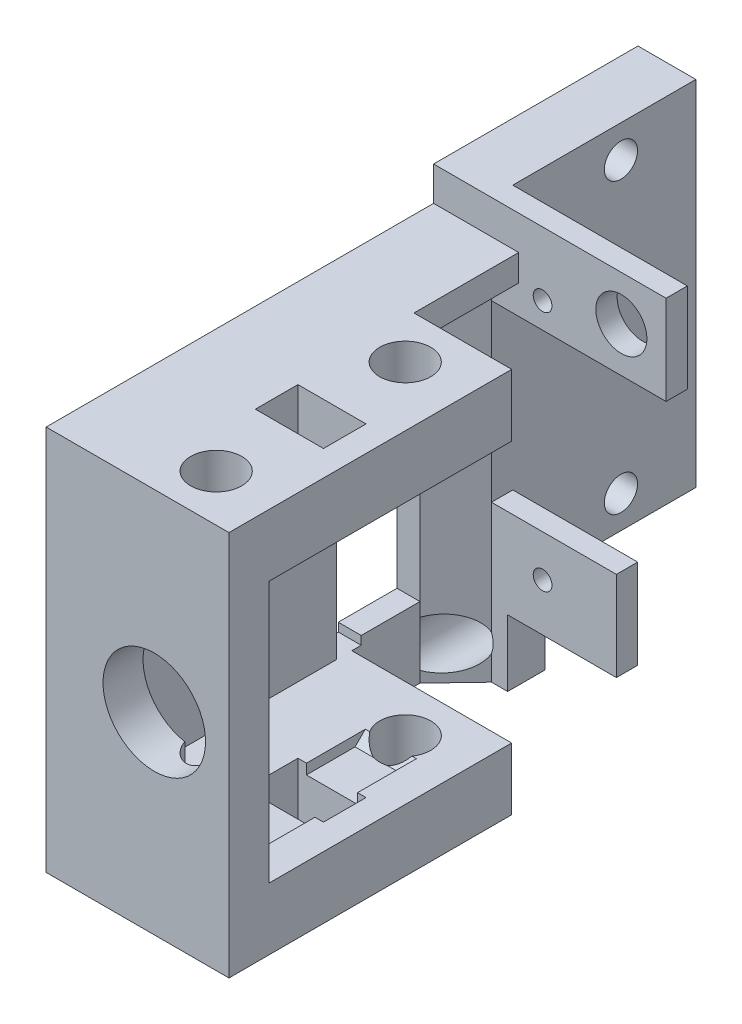
SolidWorks part; units mm, degrees
ref_plane "Alzado" through (0, 0, 0) normal (0, 0, 1) x (1, 0, 0)
ref_plane "Planta" through (0, 0, 0) normal (0, 1, 0) x (1, 0, 0)
ref_plane "Vista lateral" through (0, 0, 0) normal (1, 0, 0) x (0, 0, -1)
sketch "Croquis4" plane through (0, 0, 0) normal (1, 0, 0) x (0, 0, -1)
  line L1 (22.75, 22.65) -> (-22.75, 22.65)
  line L2 (22.75, 22.65) -> (22.75, -22.65)
  line L3 (22.75, -22.65) -> (-22.75, -22.65)
  line L4 (-22.75, 22.65) -> (-22.75, -22.65)
  line L5 (22.75, 22.65) -> (-22.75, -22.65) construction
  line L6 (22.75, -22.65) -> (-22.75, 22.65) construction
  point P0 (0, 0)
  dimension "D1" = 45.5
  dimension "D2" = 45.3
extrude "Saliente-Extruir3" add sketch "Croquis4" along normal blind 21.47
sketch "Croquis5" plane through (21.47, 0, 0) normal (1, 0, 0) x (0, 0, -1)
  line L0 (22.75, 22.65) -> (-22.75, 22.65) construction
  line L1 (23.0917, 15.35) -> (-18.05, 15.35)
  line L2 (23.0917, 15.35) -> (23.0917, -15.35)
  line L3 (23.0917, -15.35) -> (-18.05, -15.35)
  line L4 (-18.05, 15.35) -> (-18.05, -15.35)
  line L5 (23.0917, 15.35) -> (-18.05, -15.35) construction
  line L6 (23.0917, -15.35) -> (-18.05, 15.35) construction
  line L7 (-22.75, 22.65) -> (-22.75, -22.65) construction
  line L8 (-22.75, -22.65) -> (22.75, -22.65) construction
  point P0 (2.5209, 0)
  dimension "D1" = 7.3
  dimension "D2" = 4.7
  dimension "D3" = 7.3
extrude "Cortar-Extruir2" cut sketch "Croquis5" against normal blind 18.77
sketch "Croquis6" plane through (0, 22.65, 0) normal (0, 1, 0) x (1, 0, 0)
  line L0 (21.47, 22.75) -> (0, 22.75) construction
  line L1 (30.77, 35.05) -> (12.17, 35.05)
  line L2 (30.77, 35.05) -> (30.77, 10.45)
  line L3 (30.77, 10.45) -> (12.17, 10.45)
  line L4 (12.17, 35.05) -> (12.17, 10.45)
  line L5 (30.77, 35.05) -> (12.17, 10.45) construction
  line L6 (30.77, 10.45) -> (12.17, 35.05) construction
  line L7 (21.47, 22.75) -> (21.47, -22.75) construction
  point P0 (21.47, 22.75)
  dimension "D1" = 12.3
  dimension "D2" = 9.3
extrude "Cortar-Extruir3" cut sketch "Croquis6" against normal blind 18.77
sketch "Croquis7" plane through (0, 22.65, 0) normal (0, 1, 0) x (1, 0, 0)
  line L0 (21.47, -22.75) -> (0, -22.75) construction
  line L1 (21.47, 10.45) -> (21.47, -22.75) construction
  line L2 (12.17, 10.45) -> (21.47, 10.45) construction
  circle A0 centre (14.47, -17.25) radius 3
  circle A1 centre (14.47, 4.95) radius 3
  dimension "D4" = 6
  dimension "D5" = 6
  dimension "D1" = 5.5
  dimension "D2" = 7
  dimension "D3" = 5.5
extrude "Cortar-Extruir4" cut sketch "Croquis7" against normal blind 58.77
sketch "Croquis8" plane through (0, 0, 22.75) normal (0, 0, 1) x (1, 0, 0)
  line L0 (0, 22.65) -> (0, -22.65) construction
  circle A0 centre (12.7, 0) radius 6.02
  dimension "D2" = 12.04
  dimension "D1" = 12.7
extrude "Cortar-Extruir5" cut sketch "Croquis8" against normal blind 58.77
sketch "Croquis9" plane through (0, 15.35, 0) normal (0, -1, 0) x (1, 0, 0)
  line L0 (14.47, -4.95) -> (14.47, 17.0717) construction
  line L1 (17.47, 17.25) -> (17.47, -4.95) construction
  line L2 (17.47, -4.95) -> (11.47, -4.95) construction
  line L3 (11.47, -4.95) -> (11.47, 17.25) construction
  line L4 (11.47, 17.25) -> (17.47, 17.25) construction
  line L6 (17.47, 14.2208) -> (11.47, 14.2208)
  line L7 (17.47, 14.2208) -> (17.47, -2.0991)
  line L8 (17.47, -2.0991) -> (11.47, -2.0991)
  line L9 (11.47, 14.2208) -> (11.47, -2.0991)
  line L10 (17.47, 14.2208) -> (11.47, -2.0991) construction
  line L11 (17.47, -2.0991) -> (11.47, 14.2208) construction
  arc A0 (11.5786, 18.05) -> (17.3614, 18.05) centre (14.47, 17.25) ccw construction
  circle A1 centre (14.47, -4.95) radius 3 construction
  point P10 (14.47, 6.0608)
extrude "Cortar-Extruir7" cut sketch "Croquis9" against normal blind 1.2
chamfer "Chaflán1" distance 1.2 angle 45 3 edges at (16.437, 15.35, -2.0991) (12.503, 15.35, -2.0991) (14.47, 15.35, 14.2208)
sketch "Croquis10" plane through (0, 22.65, 0) normal (0, 1, 0) x (1, 0, 0)
  line L0 (14.47, 4.95) -> (14.47, -17.25) construction
  line L1 (14.47, -17.25) -> (11.47, -17.25) construction
  line L2 (11.47, -17.25) -> (11.47, 4.95) construction
  line L3 (11.47, 4.95) -> (17.47, 4.95) construction
  line L4 (17.47, 4.95) -> (17.47, -17.25) construction
  line L5 (17.47, -17.25) -> (14.47, -17.25) construction
  line L7 (18.47, -8.65) -> (10.47, -8.65)
  line L8 (18.47, -8.65) -> (18.47, -3.65)
  line L9 (18.47, -3.65) -> (10.47, -3.65)
  line L10 (10.47, -8.65) -> (10.47, -3.65)
  line L11 (18.47, -8.65) -> (10.47, -3.65) construction
  line L12 (18.47, -3.65) -> (10.47, -8.65) construction
  circle A0 centre (14.47, -17.25) radius 3 construction
  circle A1 centre (14.47, 4.95) radius 3 construction
  point P4 (14.47, -6.15)
  dimension "D1" = 5
  dimension "D2" = 8
extrude "Cortar-Extruir8" cut sketch "Croquis10" against normal blind 71.2
sketch "Croquis11" plane through (0, -15.35, 0) normal (0, 1, 0) x (1, 0, 0)
  line L0 (17.47, 4.95) -> (17.47, -17.25) construction
  line L1 (17.47, -17.25) -> (11.47, -17.25) construction
  line L2 (11.47, -17.25) -> (11.47, 4.95) construction
  line L3 (11.47, 4.95) -> (14.47, 4.95) construction
  line L4 (14.47, 4.95) -> (14.47, -17.25) construction
  line L6 (17.47, -14.3591) -> (11.47, -14.3591)
  line L7 (17.47, -14.3591) -> (17.47, 2.0591)
  line L8 (17.47, 2.0591) -> (11.47, 2.0591)
  line L9 (11.47, -14.3591) -> (11.47, 2.0591)
  line L10 (17.47, -14.3591) -> (11.47, 2.0591) construction
  line L11 (17.47, 2.0591) -> (11.47, -14.3591) construction
  circle A0 centre (14.47, 4.95) radius 3 construction
  arc A1 (17.3614, -18.05) -> (11.5786, -18.05) centre (14.47, -17.25) ccw construction
  point P9 (14.47, -6.15)
extrude "Cortar-Extruir9" cut sketch "Croquis11" against normal blind 1.2
chamfer "Chaflán2" distance 1.2 angle 45 4 edges at (12.5692, -15.35, -2.0591) (16.3708, -15.35, -2.0591) (12.5692, -15.35, 14.3591) (16.3708, -15.35, 14.3591)
sketch "Croquis12" plane through (2.7, 0, 0) normal (1, 0, 0) x (0, 0, -1)
  line L0 (8.65, 15.35) -> (8.65, -15.35)
  line L1 (22.75, 15.35) -> (-18.05, 15.35) construction
  line L2 (-18.05, -15.35) -> (22.75, -15.35) construction
  line L3 (-18.05, 15.35) -> (-18.05, -15.35) construction
  line L4 (8.65, -15.35) -> (11.5547, -15.35)
  line L5 (-18.05, -15.35) -> (22.75, -15.35) construction
  line L6 (11.5547, -15.35) -> (11.5547, -14.35)
  line L7 (11.5547, -14.35) -> (18.45, -14.35)
  line L8 (18.45, -14.35) -> (18.45, 15.35)
  line L9 (22.75, 15.35) -> (10.45, 15.35) construction
  line L10 (18.45, 15.35) -> (8.65, 15.35)
  line L11 (22.75, 15.35) -> (22.75, -15.35) construction
  dimension "D1" = 26.7
  dimension "D2" = 2.9047
  dimension "D3" = 4.3
  dimension "D4" = 1
extrude "Cortar-Extruir12" cut sketch "Croquis12" against normal blind 11.2
sketch "Croquis14" plane through (2.7, 0, 0) normal (1, 0, 0) x (0, 0, -1)
  line L0 (22.75, 15.35) -> (10.15, 15.35) construction
  line L1 (22.75, 15.35) -> (22.75, -15.35) construction
  line L2 (8.65, 15.35) -> (-18.05, 15.35) construction
  line L3 (10.15, 15.35) -> (5.15, 15.35)
  line L4 (5.15, 15.35) -> (10.15, 20.35)
  line L5 (10.15, 20.35) -> (10.15, 15.35)
  dimension "D1" = 12.6
  dimension "D2" = 0
  dimension "D3" = 5
  dimension "D4" = 5
extrude "Cortar-Extruir14" cut sketch "Croquis14" along normal blind 7
sketch "Croquis15" plane through (12.17, 0, 0) normal (1, 0, 0) x (0, 0, -1)
  line L0 (22.75, 22.65) -> (22.75, 15.35) construction
  line L1 (10.45, 15.35) -> (22.75, 15.35)
  line L2 (10.45, 15.35) -> (10.45, 19.55)
  line L3 (10.45, 19.55) -> (22.75, 19.55)
  line L4 (22.75, 15.35) -> (22.75, 19.55)
  line L5 (22.75, 22.65) -> (10.45, 22.65) construction
  dimension "D1" = 3.1
extrude "Cortar-Extruir15" cut sketch "Croquis15" against normal up to surface (9.47 mm away) up to face at (2.7, -4.7833, -17.5849)
sketch "Croquis16" plane through (0, 0, -10.15) normal (0, 0, 1) x (1, 0, 0)
  line L4 (2.7, 20.35) -> (2.7, 15.35)
  line L5 (2.7, 15.35) -> (9.7, 15.35)
  line L6 (9.7, 15.35) -> (9.7, 20.35)
  line L7 (9.7, 20.35) -> (2.7, 20.35)
  line L8 (2.7, 20.35) -> (2.7, 15.35)
  line L9 (2.7, 15.35) -> (9.7, 15.35)
  line L10 (9.7, 15.35) -> (9.7, 20.35)
  line L11 (9.7, 20.35) -> (2.7, 20.35)
  dimension "D1" = 0
extrude "Cortar-Extruir17" cut sketch "Croquis16" against normal up to surface (0.3 mm away) contours L8 L9 L10 L11 up to face at (12.1133, 19.1833, -10.45)
sketch "Croquis17" plane through (0, 0, -10.45) normal (0, 0, -1) x (-1, 0, 0)
  line L4 (-9.7, 19.55) -> (-2.7, 19.55)
  line L5 (-9.7, 20.35) -> (-9.7, 19.55)
  line L6 (-2.7, 20.35) -> (-9.7, 20.35)
  line L7 (-2.7, 19.55) -> (-2.7, 20.35)
  line L8 (-9.7, 19.55) -> (-2.7, 19.55)
  line L9 (-9.7, 20.35) -> (-9.7, 19.55)
  line L10 (-2.7, 20.35) -> (-9.7, 20.35)
  line L11 (-2.7, 19.55) -> (-2.7, 20.35)
  dimension "D1" = 0
extrude "Saliente-Extruir4" add sketch "Croquis17" against normal blind 3
sketch "Croquis18" plane through (0, 19.55, 0) normal (0, -1, 0) x (1, 0, 0)
  line L1 (2.7, -22.75) -> (24.5194, -22.75)
  line L2 (2.7, -22.75) -> (2.7, -10.45)
  line L3 (2.7, -10.45) -> (24.5194, -10.45)
  line L4 (24.5194, -22.75) -> (24.5194, -10.45)
  point P5 (24.5194, -11.6139)
  dimension "D1" = 12.3
extrude "Cortar-Extruir18" cut sketch "Croquis18" along normal blind 53
sketch "Croquis19" plane through (2.7, 0, 0) normal (1, 0, 0) x (0, 0, -1)
  line L0 (18.45, -14.35) -> (11.5547, -14.35) construction
  line L1 (11.5547, -14.35) -> (11.5547, -15.35) construction
  line L2 (11.5547, -15.35) -> (18.45, -15.35) construction
  line L3 (18.45, -15.35) -> (18.45, -14.35) construction
  line L4 (18.45, -14.35) -> (18.45, -14.85) construction
  line L5 (18.45, -14.85) -> (11.5547, -14.85) construction
  line L6 (18.45, -14.85) -> (53.9616, -14.85) construction
  line L7 (22.75, 18.5445) -> (22.75, -14.85) construction
  line L8 (22.75, 19.55) -> (22.75, -22.65) construction
  line L9 (22.75, -14.85) -> (53.9616, -14.85) construction
  line L11 (22.75, -14.85) -> (46.75, -14.85)
  line L12 (22.75, -14.85) -> (22.75, 26.65)
  line L13 (22.75, 26.65) -> (46.75, 26.65)
  line L14 (46.75, -14.85) -> (46.75, 26.65)
  dimension "D1" = 41.5
  dimension "D2" = 24
extrude "Saliente-Extruir5" add sketch "Croquis19" along normal blind 4.1 and the other way up to surface (2.7 mm away) other way up to face at (0, -4.7833, -12.8849)
sketch "Croquis21" plane through (6.8, 0, 0) normal (1, 0, 0) x (0, 0, -1)
  line L1 (22.75, 26.65) -> (25.25, 26.65)
  line L2 (22.75, 26.65) -> (22.75, 16.15)
  line L3 (22.75, 16.15) -> (25.25, 16.15)
  line L4 (25.25, 26.65) -> (25.25, 16.15)
  line L5 (22.75, -14.85) -> (25.25, -14.85)
  line L6 (22.75, -14.85) -> (22.75, -4.35)
  line L7 (22.75, -4.35) -> (25.25, -4.35)
  line L8 (25.25, -14.85) -> (25.25, -4.35)
  dimension "D1" = 2.5
  dimension "D2" = 10.5
  dimension "D3" = 2.5
  dimension "D4" = 10.5
extrude "Saliente-Extruir6" add sketch "Croquis21" along normal blind 20.5
sketch "Croquis22" plane through (6.8, 0, 0) normal (1, 0, 0) x (0, 0, -1)
  line L0 (46.75, -14.85) -> (46.75, 26.65) construction
  line L2 (46.75, 26.65) -> (25.25, 26.65) construction
  line L3 (25.25, -14.85) -> (46.75, -14.85) construction
  circle A0 centre (37.95, 22.85) radius 1.95
  circle A1 centre (37.95, -11.05) radius 1.95
  dimension "D1" = 3.9
  dimension "D5" = 3.9
  dimension "D2" = 8.8
  dimension "D3" = 3.8
  dimension "D4" = 3.8
extrude "Cortar-Extruir19" cut sketch "Croquis22" against normal blind 20.5
sketch "Croquis23" plane through (0, 0, -10.45) normal (0, 0, -1) x (-1, 0, 0)
  line L0 (-21.47, -15.35) -> (-21.47, -22.65) construction
  line L1 (-21.47, -22.2717) -> (-31.2653, -22.2717)
  line L2 (-21.47, -22.2717) -> (-21.47, -1.4695)
  line L3 (-21.47, -1.4695) -> (-31.2653, -1.4695)
  line L4 (-31.2653, -22.2717) -> (-31.2653, -1.4695)
extrude "Cortar-Extruir20" cut sketch "Croquis23" along normal blind 20.5
sketch "Croquis24" plane through (0, 0, -25.25) normal (0, 0, -1) x (-1, 0, 0)
  line L0 (-21.47, -14.85) -> (-21.47, -4.35) construction
  line L1 (-21.47, -14.85) -> (-6.8, -14.85) construction
  line L3 (-27.3, 16.15) -> (-6.8, 16.15) construction
  line L4 (-6.8, 16.15) -> (-6.8, 26.65) construction
  line L5 (-6.8, -14.85) -> (-6.8, -4.35) construction
  circle A0 centre (-12.8, -9.25) radius 1.1
  circle A1 centre (-12.8, 19.15) radius 1.1
  dimension "D3" = 2.2
  dimension "D4" = 2.2
  dimension "D1" = 8.67
  dimension "D2" = 5.6
  dimension "D5" = 3
  dimension "D6" = 6
  dimension "D7" = 6
extrude "Cortar-Extruir22" cut sketch "Croquis24" against normal up to surface (2.5 mm away) up to face at (11.74, 10.9667, -22.75)
sketch "Croquis25" plane through (0, 19.55, 0) normal (0, -1, 0) x (1, 0, 0)
  line L0 (2.7, -22.75) -> (2.7, -9.35) construction
  line L1 (12.17, -10.45) -> (10, -10.45)
  line L2 (12.17, -10.45) -> (12.17, -22.75)
  line L3 (12.17, -22.75) -> (10, -22.75)
  line L4 (10, -10.45) -> (10, -22.75)
  line L5 (2.7, -22.75) -> (11.7753, -22.75) construction
  dimension "D1" = 7.3
  dimension "D2" = 0
extrude "Cortar-Extruir23" cut sketch "Croquis25" against normal blind 13
sketch "Croquis26" plane through (0, 0, -25.25) normal (0, 0, -1) x (-1, 0, 0)
  line L1 (-27.3, 26.65) -> (-6.8, 26.65) construction
  line L2 (-27.3, 16.15) -> (-27.3, 26.65) construction
  circle A0 centre (-22.05, 21.4) radius 3
  point P2 (0, 0)
  point P5 (0, 0)
  dimension "D1" = 6
  dimension "D2" = 5.25
  dimension "D3" = 5.25
extrude "Cortar-Extruir24" cut sketch "Croquis26" against normal up to surface (2.5 mm away) up to face at (11.3783, 10.9667, -22.75)
sketch "Croquis27" plane through (2.7, 0, 0) normal (1, 0, 0) x (0, 0, -1)
  line L0 (18.45, 15.35) -> (18.45, 19.55) construction
  line L1 (22.75, 19.55) -> (9.35, 19.55) construction
sketch "Croquis28" plane through (0, 0, -22.75) normal (0, 0, 1) x (1, 0, 0)
  line L0 (6.8, 16.15) -> (6.8, 19.55) construction
  line L1 (2.7, 19.55) -> (10, 19.55) construction
  point P3 (6.8, 19.55)
sketch "Croquis30" plane through (0, 19.55, 0) normal (0, -1, 0) x (1, 0, 0)
  line L0 (2.7, -18.45) -> (6.8, -22.75)
  line L1 (6.8, -22.75) -> (2.7, -22.75)
  line L2 (2.7, -22.75) -> (2.7, -18.45)
extrude "Saliente-Extruir7" add sketch "Croquis30" along normal up to surface (42.2 mm away) up to face at (14.47, -22.65, -1.95)
sketch "Croquis31" plane through (0, 0, 0) normal (-1, 0, 0) x (0, 0, 1)
  line L1 (-22.75, -14.85) -> (-27.15, -14.85)
  line L2 (-22.75, -14.85) -> (-22.75, -22.65)
  line L3 (-22.75, -22.65) -> (-27.15, -22.65)
  line L4 (-27.15, -14.85) -> (-27.15, -22.65)
  dimension "D1" = 4.4
extrude "Saliente-Extruir8" add sketch "Croquis31" against normal blind 8.7
sketch "Croquis32" plane through (0, 0, -27.15) normal (0, 0, -1) x (-1, 0, 0)
  line L0 (0, -14.85) -> (0, -22.65) construction
  line L1 (-8.7, -22.65) -> (0, -22.65) construction
  circle A0 centre (-4, -18.65) radius 3
  dimension "D1" = 6
  dimension "D2" = 4
  dimension "D3" = 4
extrude "Cortar-Extruir25" cut sketch "Croquis32" against normal blind 8.7
